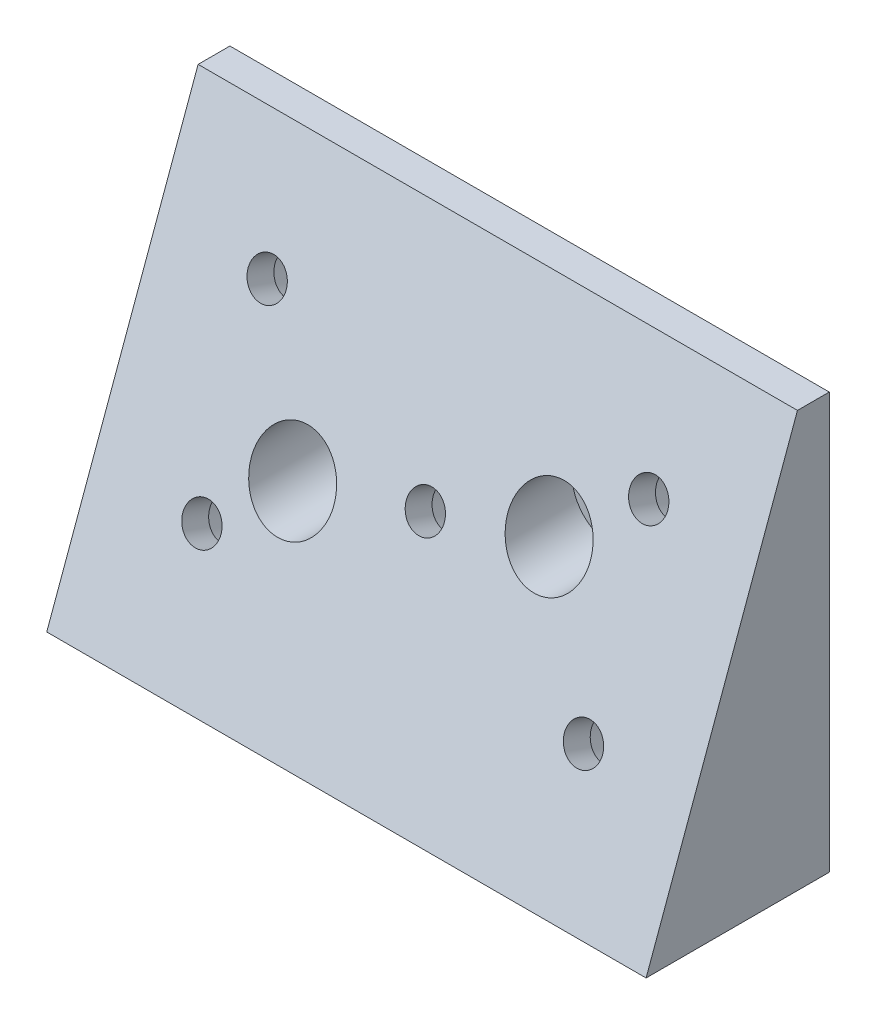
SolidWorks part; units mm, degrees
ref_plane "Front" through (0, 0, 0) normal (0, 0, 1) x (1, 0, 0)
ref_plane "Top" through (0, 0, 0) normal (0, 1, 0) x (1, 0, 0)
ref_plane "Right" through (0, 0, 0) normal (1, 0, 0) x (0, 0, -1)
sketch "Sketch1" plane through (0, 0, 0) normal (0, 0, 1) x (1, 0, 0)
  line L0 (0, 0) -> (94.2409, 0)
  line L1 (0, 0) -> (0, -65.3943)
  line L2 (0, -65.3943) -> (94.2409, -65.3943)
  line L3 (94.2409, -65.3943) -> (94.2409, 0)
extrude "Boss-Extrude1" add sketch "Sketch1" along normal blind 5
sketch "Sketch2" plane through (94.2409, 0, 0) normal (1, 0, 0) x (0, 0, -1)
  line L0 (-5, -65.3943) -> (-28.8016, -65.3943)
  line L1 (-28.8016, -65.3943) -> (-5, 0)
  line L2 (-5, 0) -> (-5, -65.3943)
extrude "Boss-Extrude2" add sketch "Sketch2" against normal blind 94.2409
sketch "Sketch3" plane through (0, 1.607, 4.4151) normal (0, 0.342, 0.9397) x (1, 0, 0)
  line L0 (94.2409, -1.7101) -> (47.2009, -1.7101)
  line L1 (94.2409, -1.7101) -> (0, -1.7101) construction
  circle A0 centre (47.2009, -35.2572) radius 3
  circle A1 centre (17.2009, -50.2572) radius 3
  circle A2 centre (17.2009, -20.2572) radius 3
  circle A3 centre (77.2009, -20.2572) radius 3
  circle A4 centre (77.2009, -50.2572) radius 3
  circle A5 centre (17.2009, -20.2572) radius 4.75
  circle A6 centre (17.2009, -50.2572) radius 4.75
  circle A7 centre (47.2009, -35.2572) radius 4.75
  circle A8 centre (77.2009, -20.2572) radius 4.75
  circle A9 centre (77.2009, -50.2572) radius 4.75
sketch "Sketch4" plane through (0, 0, 0) normal (0, 0, -1) x (-1, 0, 0)
  circle A0 centre (-64.9901, -26.9262) radius 4.5
  circle A1 centre (-28.0218, -36.1435) radius 4.5
  circle A2 centre (-64.9901, -26.9262) radius 6.5
  circle A3 centre (-28.0218, -36.1435) radius 6.5
extrude "Cut-Extrude1" cut sketch "Sketch4" against normal blind 94.2409 contours A0 | A1
extrude "Cut-Extrude2" cut sketch "Sketch4<4>" against normal blind 94.2409 from offset 4.69 contours A2 | A3 offset against normal yes
sketch "Sketch4<4>" plane through (0, 0, 0) normal (0, 0, -1) x (-1, 0, 0) same geometry as "Sketch4"
extrude "Cut-Extrude3" cut sketch "Sketch3" against normal blind 94.2409 contours A4 | A0 | A1 | A2 | A3
extrude "Cut-Extrude4" cut sketch "Sketch3<3>" against normal blind 94.2409 from offset 4.5 contours A6 | A5 | A8 | A9 | A7 offset against normal yes
sketch "Sketch3<3>" plane through (0, 1.607, 4.4151) normal (0, 0.342, 0.9397) x (1, 0, 0) same geometry as "Sketch3"
